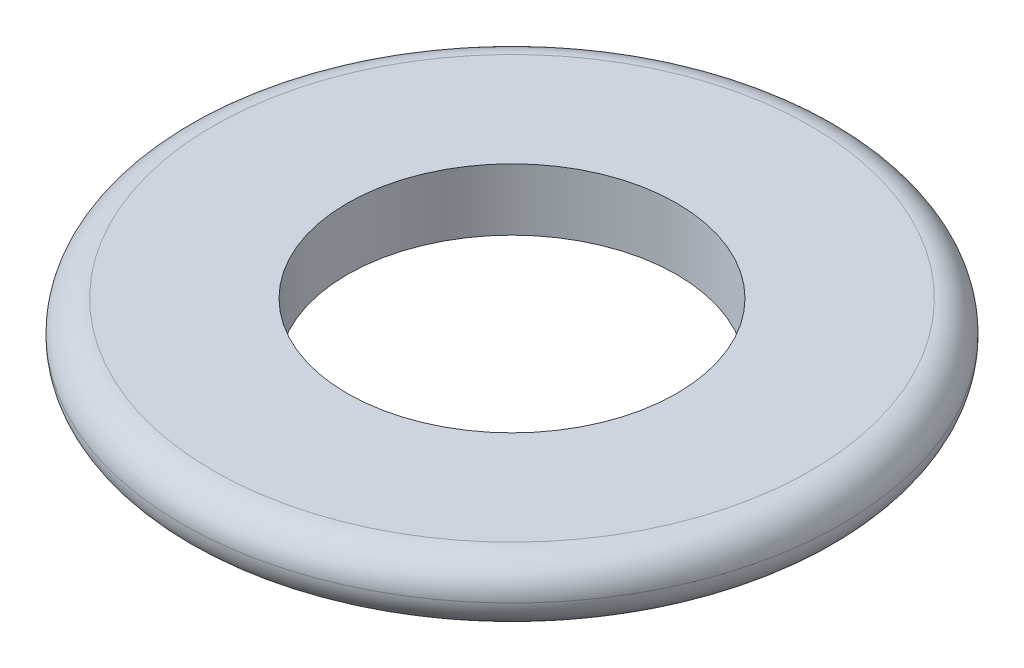
SolidWorks part; units mm, degrees
ref_plane "前视基准面" through (0, 0, 0) normal (0, 0, 1) x (1, 0, 0)
ref_plane "上视基准面" through (0, 0, 0) normal (0, 1, 0) x (1, 0, 0)
ref_plane "右视基准面" through (0, 0, 0) normal (1, 0, 0) x (0, 0, -1)
sketch "草图1" plane through (0, 0, 0) normal (0, 1, 0) x (1, 0, 0)
  circle A0 centre (0, 0) radius 4
  circle A1 centre (0, 0) radius 8
  dimension "D1" = 8
  dimension "D2" = 16
extrude "凸台-拉伸1" add sketch "草图1" along normal blind 1.5
fillet "圆角1" radius 0.75 2 edges at (0, 0, 8) (0, 1.5, 8)
